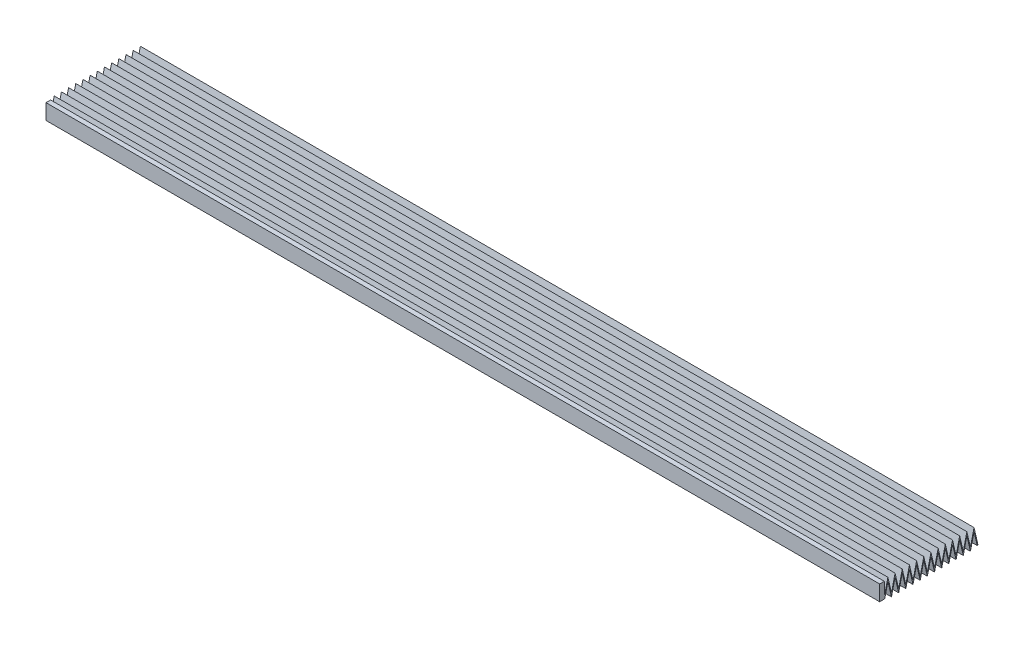
SolidWorks part; units mm, degrees
ref_plane "Front Plane" through (0, 0, 0) normal (0, 0, 1) x (1, 0, 0)
ref_plane "Top Plane" through (0, 0, 0) normal (0, 1, 0) x (1, 0, 0)
ref_plane "Right Plane" through (0, 0, 0) normal (1, 0, 0) x (0, 0, -1)
sketch "Sketch2" plane through (0, 0, 0) normal (0, 0, 1) x (1, 0, 0)
  line L1 (-270, 10) -> (270, 10)
  line L2 (-270, 10) -> (-270, 0)
  line L3 (-270, 0) -> (270, 0)
  line L4 (270, 10) -> (270, 0)
  point P4 (0, 0)
  dimension "D1" = 10
  dimension "D2" = 540
extrude "Boss-Extrude1" add sketch "Sketch2" along normal blind 3
sketch "Sketch3" plane through (270, 0, 0) normal (1, 0, 0) x (0, 0, -1)
  line L0 (0, 10) -> (60.4437, 10) construction
  line L1 (0, 0) -> (60.4437, 0) construction
  line L3 (0, 0) -> (2.3248, 10)
  line L4 (2.3248, 10) -> (4.6495, 0)
  line L5 (4.6495, 0) -> (6.9743, 10)
  line L6 (6.9743, 10) -> (9.299, 0)
  line L7 (9.299, 0) -> (11.6238, 10)
  line L8 (11.6238, 10) -> (13.9485, 0)
  line L9 (13.9485, 0) -> (16.2733, 10)
  line L10 (16.2733, 10) -> (18.5981, 0)
  line L11 (18.5981, 0) -> (20.9228, 10)
  line L12 (20.9228, 10) -> (23.2476, 0)
  line L13 (23.2476, 0) -> (25.5723, 10)
  line L14 (25.5723, 10) -> (27.8971, 0)
  line L15 (27.8971, 0) -> (30.2218, 10)
  line L16 (30.2218, 10) -> (32.5466, 0)
  line L17 (32.5466, 0) -> (34.8714, 10)
  line L18 (34.8714, 10) -> (37.1961, 0)
  line L20 (37.1961, 0) -> (39.5209, 10)
  line L21 (39.5209, 10) -> (41.8456, 0)
  line L22 (41.8456, 0) -> (44.1704, 10)
  line L23 (44.1704, 10) -> (46.4951, 0)
  line L24 (46.4951, 0) -> (48.8199, 10)
  line L25 (48.8199, 10) -> (51.1447, 0)
  line L26 (51.1447, 0) -> (53.4694, 10)
  line L27 (53.4694, 10) -> (55.7942, 0)
  line L28 (55.7942, 0) -> (58.1189, 10)
  line L29 (58.1189, 10) -> (60.4437, 0)
  line L30 (60.4437, 10) -> (60.4437, 0) construction
  line L32 (60.4437, 10) -> (60.4437, 0) construction
extrude "Extrude-Thin1" add sketch "Sketch3" against normal through all thin thin type mid plane wall 0.5
